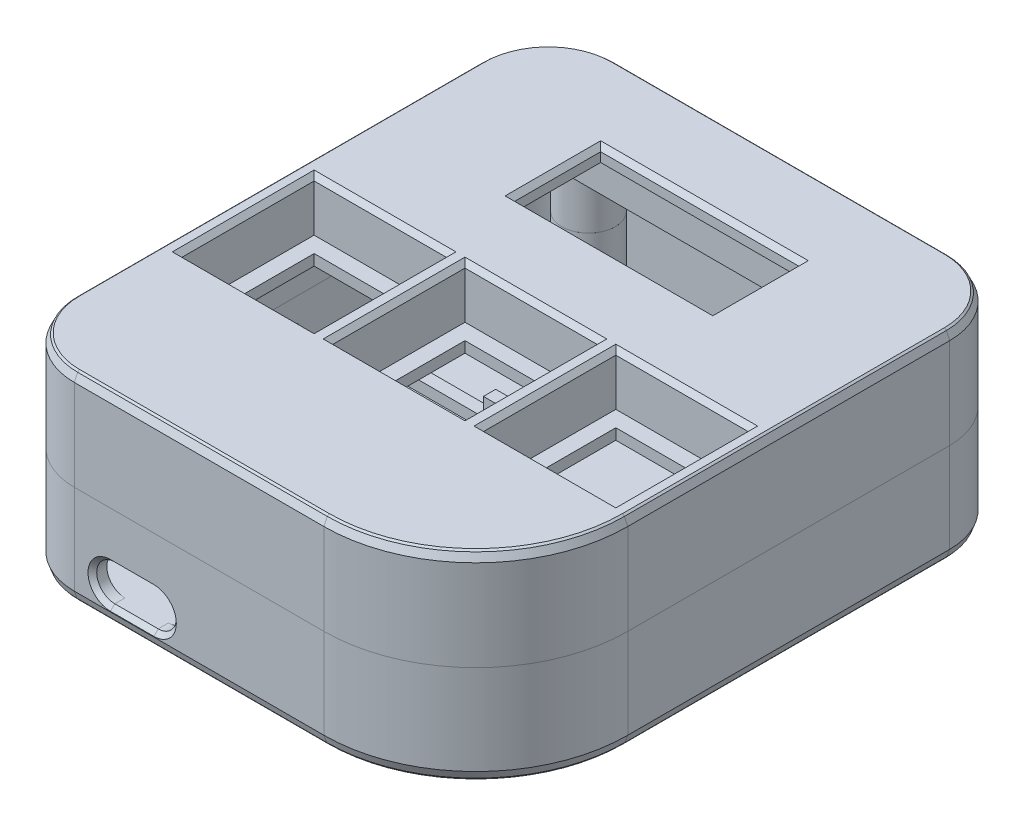
SolidWorks part; units mm, degrees
ref_plane "Front Plane" through (0, 0, 0) normal (0, 0, 1) x (1, 0, 0)
ref_plane "Top Plane" through (0, 0, 0) normal (0, 1, 0) x (1, 0, 0)
ref_plane "Right Plane" through (0, 0, 0) normal (1, 0, 0) x (0, 0, -1)
sketch "Sketch2" plane through (0, 0, 0) normal (0, 1, 0) x (1, 0, 0)
  line L1 (-32.5, -37.5) -> (32.5, -37.5)
  line L2 (-32.5, -37.5) -> (-32.5, 37.5)
  line L3 (-32.5, 37.5) -> (32.5, 37.5)
  line L4 (32.5, -37.5) -> (32.5, 37.5)
  line L5 (-32.5, -37.5) -> (32.5, 37.5) construction
  line L6 (-32.5, 37.5) -> (32.5, -37.5) construction
  point P0 (0, 0)
  dimension "D1" = 75
  dimension "D2" = 65
extrude "Body Extrude" add sketch "Sketch2" along normal blind 27.5
fillet "Small Corners" radius 9.5 3 edges at (32.5, 13.75, -37.5) (-32.5, 13.75, 37.5) (-32.5, 13.75, -37.5)
fillet "Accent Corner" radius 21 1 edges at (32.5, 13.75, 37.5)
shell "Shell1" thickness 2
sketch "E-Layout" plane through (0, 0, 0) normal (0, 1, 0) x (1, 0, 0)
  line L1 (-25, -26) -> (25, -26) construction
  line L2 (-25, -26) -> (-25, 26) construction
  line L3 (-25, 26) -> (25, 26) construction
  line L4 (25, -26) -> (25, 26) construction
  line L5 (-25, -26) -> (25, 26) construction
  line L6 (-25, 26) -> (25, -26) construction
  line L11 (-25, 26) -> (-9.7, 26) construction
  line L12 (-25, 26) -> (-25, 10.3) construction
  line L13 (-25, 10.3) -> (-9.7, 10.3) construction
  line L14 (-9.7, 26) -> (-9.7, 10.3) construction
  line L15 (25, 26) -> (-5.1, 26) construction
  line L16 (25, 26) -> (25, -26) construction
  line L17 (25, -26) -> (-5.1, -26) construction
  line L18 (-5.1, 26) -> (-5.1, -26) construction
  line L19 (-25, -35.2284) -> (-7.2, -35.2284) construction
  line L20 (-25, -35.2284) -> (-25, -14.1284) construction
  line L21 (-25, -14.1284) -> (-7.2, -14.1284) construction
  line L22 (-7.2, -35.2284) -> (-7.2, -14.1284) construction
  line L24 (-20.6, -35.2284) -> (-11.6, -35.2284) construction
  line L25 (-20.6, -35.2284) -> (-20.6, -36.7284) construction
  line L26 (-20.6, -36.7284) -> (-11.6, -36.7284) construction
  line L27 (-11.6, -35.2284) -> (-11.6, -36.7284) construction
  arc A0 (-30.5, -28) -> (-23, -35.5) centre (-23, -28) ccw construction
  point P0 (0, 0)
  point P6 (-16.1, -35.2284)
  dimension "D1" = 50
  dimension "D2" = 52
  dimension "D3" = 17.8
  dimension "D4" = 21.1
  dimension "D5" = 15.7
  dimension "D6" = 15.3
  dimension "D7" = 30.1
  dimension "D8" = 1.5
  dimension "D9" = 9
sketch "Sketch4" plane through (0, 2, 0) normal (0, 1, 0) x (1, 0, 0)
  line L0 (-23, -35.5) -> (11.5, -35.5) construction
  line L1 (-7, 27.2) -> (-5.3, 27.2)
  line L2 (-7, 27.2) -> (-7, 10.1)
  line L3 (-7, -35.5) -> (-5.3, -35.5)
  line L4 (-5.3, 27.2) -> (-5.3, -35.5)
  line L5 (-7.2, -35.2284) -> (-7.2, -14.1284) construction
  line L6 (-5.1, 26) -> (-5.1, -26) construction
  line L7 (-25, -14.1284) -> (-7.2, -14.1284) construction
  line L8 (-25, 26) -> (25, 26) construction
  line L9 (25, -26) -> (25, 26) construction
  line L10 (25.2, 27.2) -> (26.9, 27.2)
  line L11 (25.2, 27.2) -> (25.2, -29.6647)
  line L13 (26.9, 27.2) -> (26.9, -27.6283)
  line L14 (-7, -12.2284) -> (-30.5, -12.2284)
  line L16 (-7, -13.9284) -> (-25.2, -13.9284)
  line L18 (-30.5, 28) -> (-30.5, -28) construction
  line L19 (-7, -13.9284) -> (-7, -35.5)
  line L20 (-25, -26) -> (-25, 26) construction
  line L22 (-25.2, -13.9284) -> (-25.2, -35.1701)
  line L24 (-30.5, -12.2284) -> (-30.5, -28)
  line L25 (-25.2, -13.9284) -> (-25.2, -12.2284) construction
  line L26 (-17.35, 26) -> (-17.35, 10.3) construction
  line L27 (-7, 8.4) -> (-7, -12.2284)
  line L28 (-25, 10.3) -> (-9.7, 10.3) construction
  line L29 (-22.575, 24.9) -> (-12.125, 24.9) construction
  line L30 (-30.5, 10.1) -> (-7, 10.1)
  line L31 (-30.5, 10.1) -> (-30.5, 8.4)
  line L32 (-30.5, 8.4) -> (-7, 8.4)
  line L34 (-30.5, 28) -> (-30.5, -28) construction
  arc A0 (-30.5, -28) -> (-23, -35.5) centre (-23, -28) ccw construction
  arc A1 (11.5, -35.5) -> (30.5, -16.5) centre (11.5, -16.5) ccw construction
  arc A2 (25.2, -29.6647) -> (26.9, -27.6283) centre (11.5, -16.5) ccw
  arc A3 (-30.5, -28) -> (-25.2, -35.1701) centre (-23, -28) ccw
  circle A4 centre (-22.575, 23.5) radius 1.4
  circle A5 centre (-12.125, 23.5) radius 1.4
  point P45 (-17.35, 10.3)
  dimension "D8" = 2.8
  dimension "D1" = 0.2
  dimension "D2" = 0.2
  dimension "D3" = 1.2
  dimension "D4" = 0.2
  dimension "D5" = 0.2
  dimension "D6" = 0.2
  dimension "D7" = 10.45
  dimension "D9" = 1.1
  dimension "D11" = 0.2
extrude "E-Mounting" add sketch "Sketch4" along normal blind 5
sketch "Sketch6" plane through (0, 7, 0) normal (0, 1, 0) x (1, 0, 0)
  line L0 (-7, -12.2284) -> (-30.5, -12.2284) construction
  line L1 (-11.1, -12.2284) -> (-21.1, -12.2284)
  line L2 (-11.1, -12.2284) -> (-11.1, -13.9284)
  line L3 (-11.1, -13.9284) -> (-21.1, -13.9284)
  line L4 (-21.1, -12.2284) -> (-21.1, -13.9284)
  line L5 (-25.2, -13.9284) -> (-7, -13.9284) construction
  line L6 (-25.2, -13.9284) -> (-7, -13.9284) construction
  line L7 (-7, -13.9284) -> (-7, -35.5) construction
  line L8 (-7, -26) -> (-5.3, -26)
  line L9 (-7, -26) -> (-7, -35.5)
  line L10 (-7, -35.5) -> (-5.3, -35.5)
  line L11 (-5.3, -26) -> (-5.3, -35.5)
  line L12 (-5.3, -35.5) -> (-5.3, 27.2) construction
  line L13 (-7, 10.1) -> (-30.5, 10.1) construction
  line L14 (-22.35, 10.1) -> (-12.35, 10.1)
  line L15 (-22.35, 10.1) -> (-22.35, 8.4)
  line L16 (-22.35, 8.4) -> (-12.35, 8.4)
  line L17 (-12.35, 10.1) -> (-12.35, 8.4)
  line L18 (-30.5, 8.4) -> (-7, 8.4) construction
  line L19 (-23, -35.5) -> (11.5, -35.5) construction
  line L20 (-25, -26) -> (25, -26) construction
  line L23 (-17.35, 10.1) -> (-17.35, 8.4) construction
  line L24 (-9.7, 26) -> (-9.7, 10.3) construction
  line L25 (-25, -26) -> (-25, 26) construction
  point P8 (-16.1, -13.9284)
  dimension "D1" = 10
  dimension "D3" = 10
extrude "Wire Routes" cut sketch "Sketch6" against normal blind 2.5
sketch "Sketch5" plane through (0, 2, 0) normal (0, 1, 0) x (1, 0, 0)
  line L0 (-25, 26) -> (25, 26) construction
  line L1 (-25, 10.3) -> (-9.7, 10.3) construction
  circle A0 centre (-17.35, 23.5) radius 1.25
  point P7 (-17.35, 10.3)
  dimension "D1" = 2.5
  dimension "D2" = 2.5
extrude "Mic Opening" cut sketch "Sketch5" against normal up to next
sketch "Sketch11" plane through (0, 27.5, 0) normal (0, 1, 0) x (1, 0, 0)
  line L0 (-13.75, 20) -> (13.75, 20) construction
  line L1 (-13.75, 26) -> (13.75, 26)
  line L2 (-13.75, 26) -> (-13.75, 14)
  line L3 (-13.75, 14) -> (13.75, 14)
  line L4 (13.75, 26) -> (13.75, 14)
  line L5 (-30.05, 2.7) -> (-11.65, 2.7)
  line L6 (-30.05, 2.7) -> (-30.05, -15.7)
  line L7 (-30.05, -15.7) -> (-11.65, -15.7)
  line L8 (-11.65, 2.7) -> (-11.65, -15.7)
  line L9 (-9.2, 2.7) -> (9.2, 2.7)
  line L10 (-9.2, 2.7) -> (-9.2, -15.7)
  line L11 (-9.2, -15.7) -> (9.2, -15.7)
  line L12 (9.2, 2.7) -> (9.2, -15.7)
  line L13 (11.65, 2.7) -> (30.05, 2.7)
  line L14 (11.65, 2.7) -> (11.65, -15.7)
  line L15 (11.65, -15.7) -> (30.05, -15.7)
  line L16 (30.05, 2.7) -> (30.05, -15.7)
  line L17 (23, 37.5) -> (-23, 37.5) construction
  line L18 (0, 37.5) -> (0, -37.5) construction
  line L19 (-23, -37.5) -> (11.5, -37.5) construction
  line L20 (-32.5, -6.5) -> (32.5, -6.5) construction
  line L21 (-32.5, 28) -> (-32.5, -28) construction
  line L22 (32.5, -16.5) -> (32.5, 28) construction
  point P21 (-9.2, -6.5)
  point P26 (0, 20)
  point P27 (0, 2.7)
  point P34 (-30.05, -6.5)
  point P35 (11.65, -6.5)
  dimension "D1" = 27.5
  dimension "D2" = 12
  dimension "D3" = 17.5
  dimension "D4" = 18.4
  dimension "D5" = 2.45
  dimension "D6" = 2.45
  dimension "D7" = 31
extrude "Front Cutouts" cut sketch "Sketch11" against normal up to next
sketch "Sketch12" plane through (0, 25.5, 0) normal (0, -1, 0) x (1, 0, 0)
  line L0 (-30.5, -28) -> (-30.5, 28) construction
  line L1 (-30.5, -5.2) -> (30.5, -5.2)
  line L3 (-30.05, -2.7) -> (-11.65, -2.7)
  line L5 (30.5, 16.5) -> (30.5, -28) construction
  line L6 (-11.65, -2.7) -> (-30.05, -2.7) construction
  line L7 (-30.05, 15.7) -> (-11.65, 15.7) construction
  line L8 (-30.05, 15.7) -> (-11.65, 15.7)
  line L10 (-30.5, 18.2) -> (30.4238, 18.2)
  line L12 (30.05, 15.7) -> (30.05, -2.7) construction
  line L13 (11.65, -2.7) -> (11.65, 15.7) construction
  line L14 (9.2, 15.7) -> (9.2, -2.7) construction
  line L15 (-9.2, -2.7) -> (-9.2, 15.7) construction
  line L16 (-11.65, 15.7) -> (-11.65, -2.7) construction
  line L17 (-30.05, -2.7) -> (-30.05, 15.7) construction
  line L18 (30.05, 15.7) -> (30.05, -2.7)
  line L19 (30.5, 16.5) -> (30.5, -5.2)
  line L20 (11.65, -2.7) -> (11.65, 15.7)
  line L21 (9.2, 15.7) -> (9.2, -2.7)
  line L22 (-9.2, -2.7) -> (-9.2, 15.7)
  line L23 (-11.65, 15.7) -> (-11.65, -2.7)
  line L24 (-30.05, -2.7) -> (-30.05, 15.7)
  line L25 (-30.5, -28) -> (-30.5, 18.2)
  line L26 (11.65, -2.7) -> (30.05, -2.7)
  line L27 (11.65, 15.7) -> (30.05, 15.7)
  line L28 (-9.2, 15.7) -> (9.2, 15.7)
  line L29 (-9.2, -2.7) -> (9.2, -2.7)
  arc A0 (30.5, 16.5) -> (11.5, 35.5) centre (11.5, 16.5) ccw construction
  arc A1 (30.5, 16.5) -> (30.4238, 18.2) centre (11.5, 16.5) ccw
  line M13 (-30.05, -2.7) -> (-30.05, 15.7)
  line M14 (-30.05, 15.7) -> (-11.65, 15.7)
  line M15 (-11.65, 15.7) -> (-11.65, -2.7)
  line M16 (-11.65, -2.7) -> (-30.05, -2.7)
  line M17 (-9.2, -2.7) -> (-9.2, 15.7)
  line M18 (-9.2, 15.7) -> (9.2, 15.7)
  line M19 (9.2, 15.7) -> (9.2, -2.7)
  line M20 (9.2, -2.7) -> (-9.2, -2.7)
  line M21 (11.65, -2.7) -> (11.65, 15.7)
  line M22 (11.65, 15.7) -> (30.05, 15.7)
  line M23 (30.05, 15.7) -> (30.05, -2.7)
  line M24 (30.05, -2.7) -> (11.65, -2.7)
  line M27 (-30.5, 28) -> (-30.5, -28)
  line M31 (30.5, -28) -> (30.5, 16.5)
  arc M37 (30.5, 16.5) -> (11.5, 35.5) centre (11.5, 16.5) ccw
  dimension "D1" = 2.5
  dimension "D2" = 2.5
extrude "Switch Supports" add sketch "Sketch12" along normal blind 5.2 contours L10 L1 M27 M31 M37 M16 M13 M14 M15 M20 M17 M18 M19 M24 M21 M22 M23
sketch "Sketch13" plane through (0, 20.3, 0) normal (0, -1, 0) x (1, 0, 0)
  line L0 (-30.05, -2.7) -> (-11.65, 15.7) construction
  line L1 (-9.2, -2.7) -> (9.2, 15.7) construction
  line L2 (11.65, -2.7) -> (30.05, 15.7) construction
  line L3 (-30.5, 18.2) -> (30.4238, 18.2) construction
  line L4 (-27.85, -0.5) -> (-13.85, -0.5)
  line L5 (-27.85, -0.5) -> (-27.85, 13.5)
  line L6 (-27.85, 13.5) -> (-13.85, 13.5)
  line L7 (-13.85, -0.5) -> (-13.85, 13.5)
  line L8 (-27.85, -0.5) -> (-13.85, 13.5) construction
  line L9 (-27.85, 13.5) -> (-13.85, -0.5) construction
  line L10 (-7, -0.5) -> (7, -0.5)
  line L11 (-7, -0.5) -> (-7, 13.5)
  line L12 (-7, 13.5) -> (7, 13.5)
  line L13 (7, -0.5) -> (7, 13.5)
  line L14 (-7, -0.5) -> (7, 13.5) construction
  line L15 (-7, 13.5) -> (7, -0.5) construction
  line L16 (13.85, -0.5) -> (27.85, -0.5)
  line L17 (13.85, -0.5) -> (13.85, 13.5)
  line L18 (13.85, 13.5) -> (27.85, 13.5)
  line L19 (27.85, -0.5) -> (27.85, 13.5)
  line L20 (13.85, -0.5) -> (27.85, 13.5) construction
  line L21 (13.85, 13.5) -> (27.85, -0.5) construction
  line L22 (-30.5, -5.2) -> (30.5, -5.2)
  line L23 (-30.5, -5.2) -> (-30.5, 18.2)
  line L24 (-30.5, 18.2) -> (30.4238, 18.2)
  line L25 (30.5, -5.2) -> (30.5, 16.5)
  arc A0 (30.5, 16.5) -> (30.4238, 18.2) centre (11.5, 16.5) ccw construction
  arc A1 (30.5, 16.5) -> (30.4238, 18.2) centre (11.5, 16.5) ccw
  point P12 (-20.85, 6.5)
  point P17 (0, 6.5)
  point P22 (20.85, 6.5)
  dimension "D1" = 14
extrude "Switch Mounts" add sketch "Sketch13" along normal blind 1.5
sketch "Sketch14" plane through (0, 25.5, 0) normal (0, -1, 0) x (1, 0, 0)
  line L0 (-30.5, -28) -> (-30.5, -5.2) construction
  line L1 (-30.5, -13.8) -> (30.5, -13.8)
  line L2 (-30.5, -13.8) -> (-30.5, -12.6)
  line L3 (-30.5, -12.6) -> (30.5, -12.6)
  line L4 (30.5, -13.8) -> (30.5, -12.6)
  line L5 (30.5, -5.2) -> (30.5, -28) construction
  line L6 (-13.75, -14) -> (13.75, -14) construction
  line L7 (13.75, -26) -> (-13.75, -26) construction
  line L8 (-30.5, -26.2) -> (30.5, -26.2)
  line L9 (-30.5, -26.2) -> (-30.5, -27.4)
  line L10 (-30.5, -27.4) -> (30.5, -27.4)
  line L11 (30.5, -26.2) -> (30.5, -27.4)
  dimension "D1" = 1.2
  dimension "D2" = 0.2
  dimension "D3" = 0.2
extrude "Screen Retainers" add sketch "Sketch14" along normal blind 4
chamfer "Bed Chamfer" distance 0.6 angle 50 33 edges at (-29.7175, 27.5, 34.7175) (-32.5, 27.5, 0) (-29.7175, 27.5, -34.7175) (0, 27.5, -37.5) (29.7175, 27.5, -34.7175) (32.5, 27.5, -5.75) (26.3492, 27.5, 31.3492) (-5.75, 27.5, 37.5) (29.7175, 0, -34.7175) (0, 0, -37.5) (-29.7175, 0, -34.7175) (-32.5, 0, 0) (-29.7175, 0, 34.7175) (-5.75, 0, 37.5) (26.3492, 0, 31.3492) (32.5, 0, -5.75) (-17.35, 0, -24.75) (30.05, 27.5, 6.5) (20.85, 27.5, -2.7) (11.65, 27.5, 6.5) (20.85, 27.5, 15.7) (9.2, 27.5, 6.5) (0, 27.5, -2.7) (-9.2, 27.5, 6.5) (0, 27.5, 15.7) (-11.65, 27.5, 6.5) (-20.85, 27.5, -2.7) (-30.05, 27.5, 6.5) (-20.85, 27.5, 15.7) (13.75, 27.5, -20) (0, 27.5, -26) (-13.75, 27.5, -20) (0, 27.5, -14)
hole_wizard "CSK for M3 Flat Head Machine Screw1" positions "3DSketch1" profile "Sketch7" countersink size "M3" standard "ANSI Metric" end condition up to next
sketch3d "3DSketch1"
  line L2 (23, 2, -35.5) -> (-23, 2, -35.5) construction
  line L3 (25, 0, 26) -> (25, 0, -26) construction
  line L6 (-5.3, 2, 35.5) -> (11.5, 2, 35.5) construction
  point P0 (-20.5, 0, -31.0761)
  point P2 (20.5, 0, -31.0761)
  point P4 (15, 0, 31.1916)
  dimension "D1" = 10
  dimension "D2" = 4.855
  dimension "D3" = 10
  dimension "D4" = 4.75
  dimension "D5" = 10
sketch "Sketch7" plane through (-20.5, 0, -31.0761) normal (1, 0, 0) x (0, 0, -1)
  line L0 (0, 0) -> (0, 2)
  line L1 (0, 2) -> (1.7, 2)
  line L2 (1.7, 2) -> (1.7, 1.45)
  line L3 (1.7, 1.45) -> (3.15, 0)
  line L5 (3.15, 0) -> (0, 0)
  line L6 (-1.7, 1.45) -> (-3.15, 0) construction
  line L11 (0, -6.35) -> (0, 107.95) construction
  dimension "Thru Hole Dia." = 3.4
  dimension "Thru Hole Depth" = 2
  dimension "Near C'Sink Dia." = 6.3
  dimension "Near C'Sink Angle" = 90
sketch "Sketch10" plane through (0, 0, 35.5) normal (0, 0, -1) x (-1, 0, 0)
  line L0 (12, 4.5) -> (18, 4.5) construction
  line L1 (12, 7) -> (18, 7)
  line L2 (12, 2) -> (18, 2)
  line L3 (15, 2) -> (15, 25.5) construction
  line L4 (23, 2) -> (7, 2) construction
  line L5 (23, 25.5) -> (-11.5, 25.5) construction
  arc A0 (12, 7) -> (12, 2) centre (12, 4.5) ccw
  arc A1 (18, 2) -> (18, 7) centre (18, 4.5) ccw
  point P2 (15, 4.5)
  dimension "D1" = 6
  dimension "D2" = 5
  dimension "D3" = 2.5
extrude "USB-C" cut sketch "Sketch10" against normal up to next contours L1 A1 L2 A0
sketch "Sketch8" plane through (0, 2, 0) normal (0, 1, 0) x (1, 0, 0)
  circle A0 centre (20.5, 31.0761) radius 3.7
  circle A1 centre (15, -31.1916) radius 3.7
  circle A2 centre (-20.5, 31.0761) radius 3.7
  circle A3 centre (15, -31.1916) radius 1.7 construction
  circle A4 centre (20.5, 31.0761) radius 1.7 construction
  circle A5 centre (-20.5, 31.0761) radius 1.7 construction
  circle A6 centre (15, -31.1916) radius 1.7
  circle A7 centre (20.5, 31.0761) radius 1.7
  circle A8 centre (-20.5, 31.0761) radius 1.7
  dimension "D1" = 7.4
extrude "Screw Posts" add sketch "Sketch8" along normal up to next
chamfer "Post Chamfers" distance 1 distance2 4.65 6 edges at (20.5, 25.5, -34.7761) (20.5, 2, -34.7761) (15, 25.5, 27.4916) (15, 2, 27.4916) (-20.5, 25.5, -34.7761) (-20.5, 2, -34.7761)
sketch "Sketch17" plane through (-30.5, 0, 0) normal (1, 0, 0) x (0, 0, -1)
  line L0 (-2, 2) -> (-2, 18.8) construction
  line L5 (-4.7, 10.2) -> (0.7, 10.2) construction
  line L9 (-3.5, 7) -> (-0.5, 7) construction
  line L10 (-18.2, 18.8) -> (5.2, 18.8) construction
  line L11 (-4.9, 5.6) -> (0.9, 5.6)
  line L12 (-5.5, 4.5) -> (1.5, 4.5) construction
  line L13 (-5.5, 4.5) -> (-5.5, 11.5) construction
  line L14 (-5.5, 11.5) -> (1.5, 11.5) construction
  line L15 (1.5, 4.5) -> (1.5, 11.5) construction
  line L16 (-5.5, 4.5) -> (1.5, 11.5) construction
  line L17 (-5.5, 11.5) -> (1.5, 4.5) construction
  line L18 (-3.5, 7) -> (-3.5, 9) construction
  line L19 (-3.5, 9) -> (-0.5, 9) construction
  line L20 (-0.5, 7) -> (-0.5, 9) construction
  line L21 (-3.5, 7) -> (-0.5, 9) construction
  line L22 (-3.5, 9) -> (-0.5, 7) construction
  line L23 (0.7, 5.8) -> (0.7, 10.2) construction
  line L24 (-4.7, 5.8) -> (0.7, 5.8) construction
  line L25 (-4.7, 5.8) -> (-4.7, 10.2) construction
  line L26 (0.9, 5.6) -> (0.9, 10.4)
  line L27 (-4.9, 10.4) -> (0.9, 10.4)
  line L28 (-4.9, 5.6) -> (-4.9, 10.4)
  line L29 (-35.5, 2) -> (27.2, 2) construction
  line L30 (-4, 6) -> (0, 6) construction
  line L31 (-4, 6) -> (-4, 10) construction
  line L32 (-4, 10) -> (0, 10) construction
  line L33 (0, 6) -> (0, 10) construction
  line L34 (-4, 6) -> (0, 10) construction
  line L35 (-4, 10) -> (0, 6) construction
  line L36 (37.5, 0.7151) -> (37.5, 26.9) construction
  point P12 (-2, 8)
  point P22 (-2, 8)
  point P23 (-2, 8)
  dimension "D1" = 2.5
  dimension "D2" = 1.4
  dimension "D3" = 7
  dimension "D4" = 2
  dimension "D5" = 3
  dimension "D7" = 4
  dimension "D8" = 39.5
  dimension "D6" = 1.2
extrude "Power Switch Slot" cut sketch "Sketch17" against normal up to next contours L28 L11 L26 L27
sketch "Sketch21" plane through (-30.5, 0, 0) normal (1, 0, 0) x (0, 0, -1)
  line L0 (-8.2, 8) -> (-4, 8)
  line L2 (-4, 8) -> (-4, 6)
  line L3 (-4, 6) -> (0, 6)
  line L4 (0, 6) -> (0, 8)
  line L6 (0, 8) -> (4.2, 8)
  line L7 (4.2, 8) -> (4.2, 2)
  line L8 (4.2, 2) -> (-8.2, 2)
  line L9 (-8.2, 2) -> (-8.2, 8)
  line L10 (-4, 6) -> (-4, 10) construction
  line L11 (-4, 6) -> (0, 6) construction
  line L12 (0, 6) -> (0, 10) construction
  line L17 (8.4, 2) -> (-12.2284, 2) construction
  line L18 (8.4, 2) -> (-12.2284, 2) construction
  dimension "D1" = 12.4
  dimension "D2" = 6
extrude "Switch Spacer" add sketch "Sketch21" along normal blind 3.4
sketch "Sketch20" plane through (-27.1, 0, 0) normal (1, 0, 0) x (0, 0, -1)
  line L1 (-5.7, 8) -> (-8.2, 8)
  line L2 (-5.7, 8) -> (-5.7, 4.5)
  line L4 (-8.2, 8) -> (-8.2, 2)
  line L6 (1.7, 8) -> (4.2, 8)
  line L7 (1.7, 8) -> (1.7, 4.5)
  line L9 (4.2, 8) -> (4.2, 2)
  line L10 (1.5, 4.5) -> (1.5, 11.5) construction
  line L12 (-5.7, 4.5) -> (1.7, 4.5)
  line L14 (-8.2, 2) -> (4.2, 2)
  line L17 (-5.5, 4.5) -> (-5.5, 11.5) construction
  line L19 (-5.5, 4.5) -> (1.5, 4.5) construction
  line L20 (8.4, 2) -> (4.2, 2) construction
  dimension "D1" = 2.5
  dimension "D2" = 2.5
  dimension "D3" = 0.2
  dimension "D4" = 0.2
extrude "Switch Mount" add sketch "Sketch20" along normal blind 7
sketch "Sketch23" plane through (0, 2, 0) normal (0, 1, 0) x (1, 0, 0)
  line L0 (-20.1, -8.2) -> (-30.5, -8.2) construction
  line L1 (-20.1, 4.2) -> (-18.7, 4.2)
  line L2 (-20.1, 4.2) -> (-20.1, -8.2)
  line L3 (-20.1, -8.2) -> (-18.7, -8.2)
  line L4 (-18.7, 4.2) -> (-18.7, -8.2)
  dimension "D1" = 1.4
extrude "Switch Retainer-1" add sketch "Sketch23" along normal up to surface (2.5 mm away) up to face at (-23.6, 4.5, 2)
sketch "Sketch24" plane through (0, 4.5, 0) normal (0, 1, 0) x (1, 0, 0)
  line L1 (-20.1, 1.7) -> (-19.9, 1.7)
  line L3 (-20.1, -5.7) -> (-19.9, -5.7)
  line L4 (-19.9, 1.7) -> (-19.9, -5.7)
  line L8 (-27.1, 1.7) -> (-27.1, -5.7)
  line L9 (-27.1, -5.7) -> (-20.1, -5.7)
  line L10 (-20.1, -5.7) -> (-20.1, -8.2)
  line L11 (-20.1, -8.2) -> (-18.7, -8.2)
  line L12 (-18.7, -8.2) -> (-18.7, 4.2)
  line L13 (-18.7, 4.2) -> (-20.1, 4.2)
  line L14 (-20.1, 4.2) -> (-20.1, 1.7)
  line L15 (-20.1, 1.7) -> (-27.1, 1.7)
  line L18 (-20.1, -5.7) -> (-20.1, -8.2)
  line L19 (-20.1, -8.2) -> (-18.7, -8.2)
  line L20 (-18.7, -8.2) -> (-18.7, 4.2)
  line L21 (-18.7, 4.2) -> (-20.1, 4.2)
  line L22 (-20.1, 4.2) -> (-20.1, 1.7)
  dimension "D2" = 0.2
  dimension "D1" = 0
extrude "Switch Retainer-2" add sketch "Sketch24" along normal blind 0.4
chamfer "Internal Chamfers" distance 1 13 edges at (26.9643, 25.5, -27.4) (-26.9643, 25.5, -27.4) (0, 25.5, -27.4) (0, 25.5, -12.6) (-0.0381, 25.5, 18.2) (0, 25.5, -5.2) (-18.75, 2, 12.2284) (-18.75, 2, -8.4) (26.9, 2, 0.2142) (-7, 2, 1.9142) (-24.6, 2, -4.2) (-18.7, 2, 2) (-24.6, 2, 8.2)
chamfer "Port Chamfer" distance 0.6 24 edges at (-29.7175, 0.7151, 34.7175) (-29.7175, 26.9, 34.7175) (-32.5, 0.7151, 0) (-32.5, 26.9, 0) (-29.7175, 0.7151, -34.7175) (-29.7175, 26.9, -34.7175) (0, 0.7151, -37.5) (0, 26.9, -37.5) (29.7175, 0.7151, -34.7175) (29.7175, 26.9, -34.7175) (32.5, 0.7151, -5.75) (32.5, 26.9, -5.75) (26.3492, 0.7151, 31.3492) (26.3492, 26.9, 31.3492) (-5.75, 0.7151, 37.5) (-5.75, 26.9, 37.5) (-15, 7, 37.5) (-15, 2, 37.5) (-9.5, 4.5, 37.5) (-20.5, 4.5, 37.5) (-32.5, 8, 4.9) (-32.5, 10.4, 2) (-32.5, 8, -0.9) (-32.5, 5.6, 2)
ref_plane "Box Cut Plane" through (0, 13.75, 0) normal (0, 1, 0) x (1, 0, 0)
sketch "Sketch27" plane through (0, 13.75, 0) normal (0, 1, 0) x (1, 0, 0)
  circle A0 centre (20.5, 31.0761) radius 2.5
  circle A1 centre (15, -31.1916) radius 2.5
  circle A3 centre (-20.5, 31.0761) radius 2.5
  circle A4 centre (-20.5, 31.0761) radius 3.7 construction
  circle A5 centre (-20.5, 31.0761) radius 3.7 construction
  dimension "D1" = 5
extrude "Heatset Inserts" cut sketch "Sketch27" along normal up to surface (11.75 mm away) up to face at (0, 25.5, -32.2306)
split "Split2" trim tools "Box Cut Plane" bodies to split 124 resulting bodies 125 126
